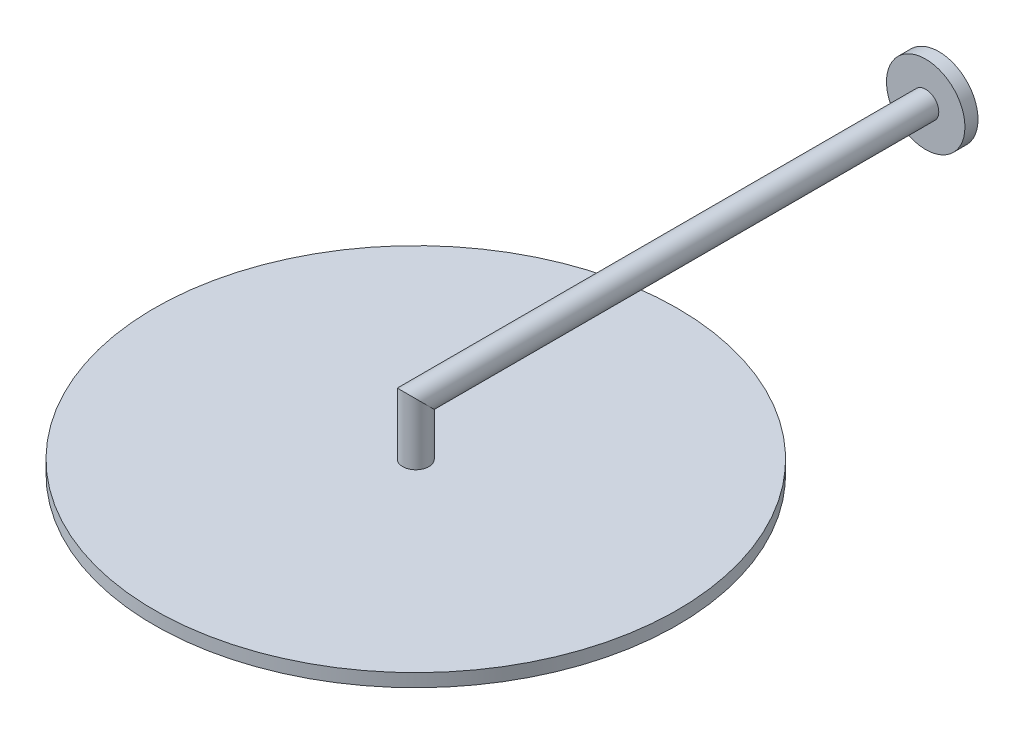
SolidWorks part; units mm, degrees
ref_plane "Спереди" through (0, 0, 0) normal (0, 0, 1) x (1, 0, 0)
ref_plane "Сверху" through (0, 0, 0) normal (0, 1, 0) x (1, 0, 0)
ref_plane "Справа" through (0, 0, 0) normal (1, 0, 0) x (0, 0, -1)
sketch "Эскиз1" plane through (0, 0, 0) normal (0, 0, 1) x (1, 0, 0)
  circle A0 centre (0, 0) radius 30
  dimension "D1" = 60
extrude "Бобышка-Вытянуть1" add sketch "Эскиз1" along normal blind 10
sketch3d "Трехмерный эскиз1"
  line L0 (0, 0, 0) -> (0, 0, 400)
  line L1 (0, 0, 400) -> (0, -40, 400)
  dimension "D1" = 400
  dimension "D2" = 40
sweep "По траектории1" add path "Трехмерный эскиз1" circular profile diameter 20 parameters "D3"=20
sketch "Эскиз7" plane through (0, -40, 0) normal (0, -1, 0) x (-1, 0, 0)
  circle A0 centre (0, -400) radius 200
  dimension "D1" = 400
extrude "Бобышка-Вытянуть2" add sketch "Эскиз7" along normal blind 10
ref_axis "Ось1" through (0, 0, 10) along (0, 0, 1)
